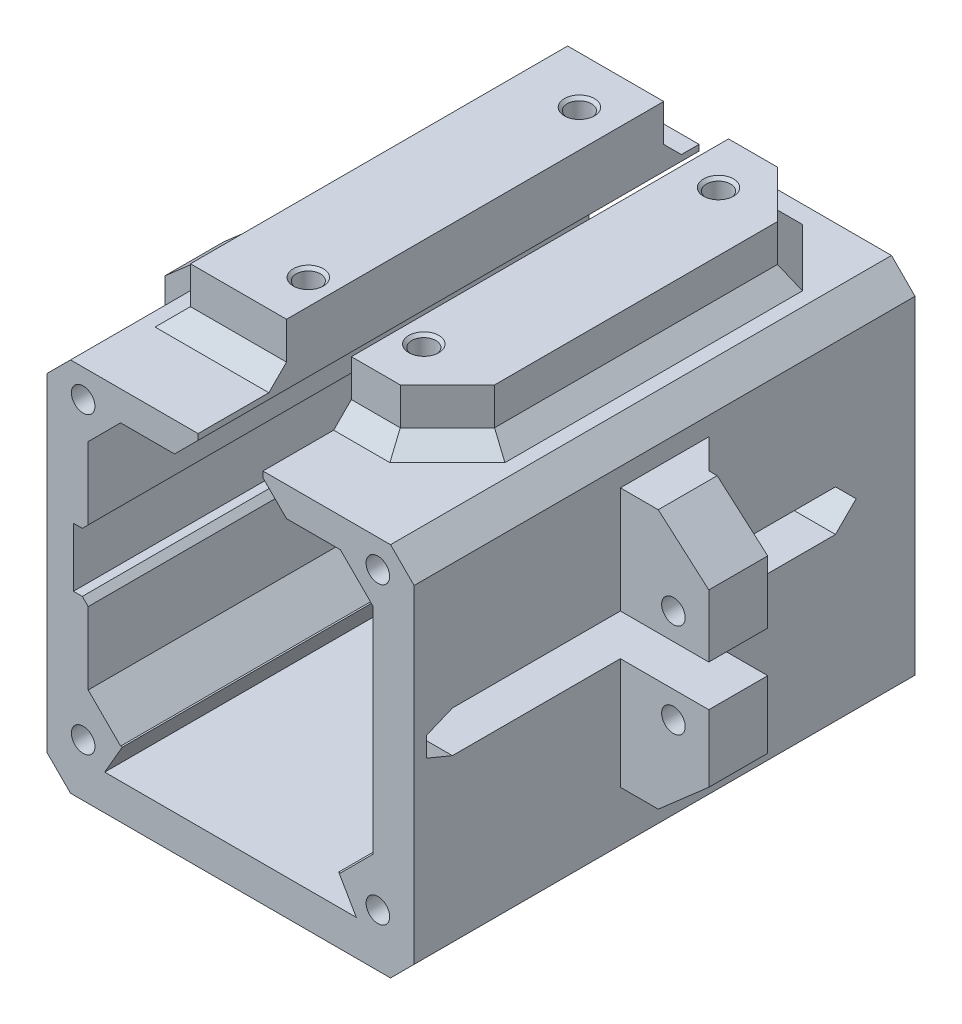
SolidWorks part; units mm, degrees
ref_plane "Front Plane" through (0, 0, 0) normal (0, 0, 1) x (1, 0, 0)
ref_plane "Top Plane" through (0, 0, 0) normal (0, 1, 0) x (1, 0, 0)
ref_plane "Right Plane" through (0, 0, 0) normal (1, 0, 0) x (0, 0, -1)
sketch "Sketch3" plane through (0, 0, 0) normal (0, 0, 1) x (1, 0, 0)
  line L0 (-20.15, 10.3748) -> (-23.65, 10.3748)
  line L1 (-23.65, 10.3748) -> (-23.65, 10.3393)
  line L2 (-23.65, 10.3393) -> (-18.1855, 4.8748)
  line L3 (-18.1855, 4.8748) -> (-21, 0)
  line L4 (-21, 0) -> (21, 0)
  line L5 (21, 0) -> (18.1855, 4.8748)
  line L6 (18.1855, 4.8748) -> (23.65, 10.3393)
  line L7 (23.65, 10.3393) -> (23.65, 10.3748)
  line L8 (23.65, 10.3748) -> (20.15, 10.3748)
  line L9 (20.15, 10.3748) -> (17.15, 7.3748)
  line L10 (17.15, 7.3748) -> (-17.15, 7.3748)
  line L11 (-17.15, 7.3748) -> (-20.15, 10.3748)
  point P12 (0, 0)
sketch "Sketch4" plane through (0, 0, 0) normal (0, 0, 1) x (1, 0, 0)
  line L3 (-18.3587, 4.9748) -> (-27, 4.9748)
  line L4 (-27, 4.9748) -> (-27, -6.2)
  line L5 (-27, -6.2) -> (27, -6.2)
  line L6 (21.3464, -0.2) -> (18.3587, 4.9748)
  line L7 (-21.3464, -0.2) -> (21.3464, -0.2)
  line L8 (-18.3587, 4.9748) -> (-21.3464, -0.2)
  line L9 (21.3464, -0.2) -> (18.3587, 4.9748)
  line L10 (-21.3464, -0.2) -> (21.3464, -0.2)
  line L11 (-18.3587, 4.9748) -> (-21.3464, -0.2)
  line L12 (27, -6.2) -> (27, 4.9748)
  line L13 (27, 4.9748) -> (18.3587, 4.9748)
  dimension "D2" = 36.7175
  dimension "D3" = 54
  dimension "D4" = 6
  dimension "D5" = 27
  dimension "D6" = 42.6928
  dimension "D7" = 60
  dimension "D8" = 11.1748
  dimension "D1" = 0.2
extrude "Boss-Extrude1" add sketch "Sketch4" along normal blind 100
sketch "Sketch6" plane through (0, 0, 100) normal (0, 0, 1) x (1, 0, 0)
  line L0 (-24.15, 4.9748) -> (-24.15, 52.4748)
  line L1 (-18.3587, 4.9748) -> (-27, 4.9748) construction
  line L2 (-24.15, 52.4748) -> (-5.5, 52.4748)
  line L3 (-5.5, 52.4748) -> (-5.5, 57.4748)
  line L4 (-5.5, 57.4748) -> (-31.15, 57.4748)
  line L5 (-31.15, 57.4748) -> (-31.15, -6.2)
  line L6 (-31.15, -6.2) -> (-24.15, -6.2)
  line L7 (-27, -6.2) -> (27, -6.2) construction
  line L8 (-24.15, -6.2) -> (-24.15, 4.9748)
  line L9 (-23.65, 46.5103) -> (-23.65, 34.3248) construction
  line L10 (-9, 51.9748) -> (-18.1855, 51.9748) construction
  line L12 (24.15, -6.2) -> (24.15, 52.4748)
  line L13 (-27, -6.2) -> (27, -6.2) construction
  line L14 (24.15, 52.4748) -> (5.5, 52.4748)
  line L15 (5.5, 52.4748) -> (5.5, 57.4748)
  line L16 (5.5, 57.4748) -> (31.15, 57.4748)
  line L17 (31.15, 57.4748) -> (31.15, -6.2)
  line L18 (31.15, -6.2) -> (24.15, -6.2)
  line L20 (23.65, 42.9748) -> (23.65, 46.5103) construction
  line L21 (5, 62.9748) -> (5, 55.9748) construction
  line L22 (-5, 55.9748) -> (-5, 62.9748) construction
  dimension "D1" = 7
  dimension "D2" = 0.5
  dimension "D3" = 0.5
  dimension "D4" = 5
  dimension "D5" = 0.5
  dimension "D6" = 5
  dimension "D7" = 0.5
  dimension "D8" = 7
  dimension "D9" = 0.5
extrude "Boss-Extrude2" add sketch "Sketch6" against normal up to surface (100 mm away) up to face at (0, 0.8874, 0)
sketch "Sketch7" plane through (31.15, 0, 0) normal (1, 0, 0) x (0, 0, -1)
  line L0 (-85, 28.7248) -> (-81.5, 25.2248)
  line L1 (-81.5, 25.2248) -> (-13.5, 25.2248)
  line L4 (-13.5, 32.2248) -> (-81.5, 32.2248)
  line L5 (-81.5, 32.2248) -> (-85, 28.7248)
  line L6 (-100, -6.2) -> (-100, 57.4748) construction
  line L7 (-13.5, 25.2248) -> (-10, 28.7248)
  line L8 (-10, 28.7248) -> (-13.5, 32.2248)
  line L9 (0, 57.4748) -> (0, -6.2) construction
  line L10 (-13.5, 25.2248) -> (0, 25.2248) construction
  line L11 (0, 32.2248) -> (-13.5, 32.2248) construction
  line L12 (0, 25.2248) -> (0, 32.2248) construction
  point P6 (0, 28.7248)
  dimension "D1" = 135
  dimension "D2" = 15
  dimension "D3" = 7
  dimension "D4" = 23.75
  dimension "D5" = 90
  dimension "D6" = 10
extrude "Cut-Extrude1" cut sketch "Sketch7" against normal blind 10
chamfer "Chamfer1" distance 5.5 angle 45 4 edges at (24.15, 4.9748, 50) (-24.15, 4.9748, 50) (-24.15, 52.4748, 50) (24.15, 52.4748, 50)
chamfer "Chamfer2" distance 4 angle 45 2 edges at (5.5, 52.4748, 50) (-5.5, 52.4748, 50)
sketch "Sketch8" plane through (0, 57.4748, 0) normal (0, 1, 0) x (1, 0, 0)
  line L0 (-5.5, -100) -> (-31.15, -100) construction
  line L1 (-21.8, -70) -> (13.8, -70)
  line L2 (-21.8, -70) -> (-21.8, -6)
  line L3 (-21.8, -6) -> (13.8, -6)
  line L4 (21.8, -62) -> (21.8, -14)
  line L5 (13.8, -70) -> (21.8, -62)
  line L6 (13.8, -6) -> (21.8, -14)
  circle A0 centre (9.8, -62) radius 2
  circle A1 centre (11.8, -14) radius 2
  circle A2 centre (-11.8, -14) radius 2
  circle A3 centre (-9.8, -62) radius 2
  point P1 (21.8, -6)
  point P3 (21.8, -70)
  dimension "D5" = 4
  dimension "D6" = 4
  dimension "D9" = 4
  dimension "D10" = 4
  dimension "D1" = 94
  dimension "D2" = 43.6
  dimension "D3" = 64
  dimension "D4" = 21.8
extrude "Boss-Extrude3" add sketch "Sketch8" along normal blind 9.3
sketch "Sketch9" plane through (0, 0, 0) normal (0, 0, 1) x (1, 0, 0)
  line L0 (-21.8, 66.7748) -> (13.8, 66.7748) construction
  line L1 (5.5, 57.4748) -> (-5.5, 57.4748)
  line L2 (5.5, 57.4748) -> (5.5, 66.7748)
  line L3 (5.5, 66.7748) -> (-5.5, 66.7748)
  line L4 (-5.5, 57.4748) -> (-5.5, 66.7748)
  line L5 (-5.5, 56.4748) -> (-5.5, 57.4748) construction
extrude "Cut-Extrude3" cut sketch "Sketch9" against normal blind 10 and the other way through all
chamfer "Chamfer3" distance 4 angle 45 4 edges at (31.15, -6.2, 50) (-31.15, -6.2, 50) (-31.15, 57.4748, 50) (31.15, 57.4748, 50)
chamfer "Chamfer4" distance 3 angle 45 8 edges at (9.65, 57.4748, 6) (17.8, 57.4748, 10) (21.8, 57.4748, 38) (17.8, 57.4748, 66) (9.65, 57.4748, 70) (-13.65, 57.4748, 6) (-13.65, 57.4748, 70) (-21.8, 57.4748, 38)
chamfer "Chamfer5" distance 3 3 edges at (27.65, 25.2248, 81.5) (27.65, 32.2248, 81.5) (27.65, 28.7248, 85)
sketch "Sketch10" plane through (0, 0, 100) normal (0, 0, 1) x (1, 0, 0)
  line L0 (-24.15, 10.4748) -> (-24.15, 46.9748) construction
  line L1 (-21.65, 23.7248) -> (-26.65, 23.7248)
  line L2 (-21.65, 23.7248) -> (-21.65, 33.7248)
  line L3 (-21.65, 33.7248) -> (-26.65, 33.7248)
  line L4 (-26.65, 23.7248) -> (-26.65, 33.7248)
  line L5 (-21.65, 23.7248) -> (-26.65, 33.7248) construction
  line L6 (-21.65, 33.7248) -> (-26.65, 23.7248) construction
  point P0 (-24.15, 28.7248)
  dimension "D1" = 5
  dimension "D2" = 10
extrude "Cut-Extrude4" cut sketch "Sketch10" against normal offset from surface (94 mm away) 6 up to face at (0, 29.896, 0)
chamfer "Chamfer7" distance 1 angle 45 1 edges at (-24.15, 28.7248, 6)
chamfer "Chamfer8" distance 1 angle 45 2 edges at (-24.15, 23.7248, 52.5) (-24.15, 33.7248, 52.5)
sketch "Sketch11" plane through (0, 66.7748, 0) normal (0, 1, 0) x (1, 0, 0)
  circle A0 centre (-11.8, -14) radius 2.05
  circle A1 centre (11.8, -14) radius 2.05
  circle A2 centre (-9.8, -62) radius 2.05
  circle A3 centre (9.8, -62) radius 2.05
  dimension "D1" = 4.1
  dimension "D2" = 4.1
  dimension "D3" = 4.1
  dimension "D4" = 4.1
extrude "Cut-Extrude5" cut sketch "Sketch11" against normal blind 10
chamfer "Chamfer9" distance 0.5 angle 45 4 edges at (11.8, 66.7748, 16.05) (-11.8, 66.7748, 16.05) (-9.8, 66.7748, 64.05) (9.8, 66.7748, 64.05)
sketch "Sketch12" plane through (0, 0, 100) normal (0, 0, 1) x (1, 0, 0)
  line L1 (-25, 52.7248) -> (25, 52.7248) construction
  line L2 (-25, 52.7248) -> (-25, 2.7248) construction
  line L3 (-25, 2.7248) -> (25, 2.7248) construction
  line L4 (25, 52.7248) -> (25, 2.7248) construction
  line L5 (24.15, 46.9748) -> (24.15, 10.4748) construction
  circle A0 centre (-25, 52.7248) radius 2
  circle A1 centre (25, 52.7248) radius 2
  circle A2 centre (-25, 2.7248) radius 2
  circle A3 centre (25, 2.7248) radius 2
  point P5 (0, 2.7248)
  point P9 (24.15, 28.7248)
  dimension "D1" = 4
  dimension "D5" = 4
  dimension "D6" = 4
  dimension "D7" = 4
  dimension "D2" = 50
  dimension "D3" = 50
  dimension "D4" = 24
extrude "Cut-Extrude6" cut sketch "Sketch12" against normal blind 30
ref_plane "Plane1" through (0, 0, 48) normal (0, 0, -1) x (-1, 0, 0)
sketch "Sketch16" plane through (0, 0, 48) normal (0, 0, -1) x (-1, 0, 0)
  line L1 (-22, -0.6752) -> (22, -0.6752)
  line L4 (22, -0.6752) -> (22, -9.2502)
  line L6 (-975.85, 28.3248) -> (49024.15, 28.3248) construction
  line L7 (24.15, 46.9748) -> (24.15, 10.4748) construction
  line L8 (22, -9.2502) -> (14.5, -17.8252)
  line L14 (-29, 50.3248) -> (-37.575, 50.3248)
  line L18 (0, -1000) -> (0, 49000) construction
  line L19 (0, 40.1361) -> (0, -40.1361) construction
  line L20 (-37.575, 50.3248) -> (-46.15, 42.8248)
  line L21 (-46.15, 42.8248) -> (-46.15, 13.8248)
  line L22 (-46.15, 13.8248) -> (-37.575, 6.3248)
  line L23 (-37.575, 6.3248) -> (-29, 6.3248)
  line L24 (-29, 6.3248) -> (-29, 50.3248)
  line L25 (37.575, 6.3248) -> (29, 6.3248)
  line L32 (14.5, -17.8252) -> (-14.5, -17.8252)
  line L33 (-14.5, -17.8252) -> (-22, -9.2502)
  line L34 (-22, -9.2502) -> (-22, -0.6752)
  line L42 (46.15, 13.8248) -> (37.575, 6.3248)
  line L43 (46.15, 42.8248) -> (46.15, 13.8248)
  line L44 (37.575, 50.3248) -> (46.15, 42.8248)
  line L45 (29, 50.3248) -> (37.575, 50.3248)
  line L46 (29, 6.3248) -> (29, 50.3248)
  line L47 (24.15, 4.1748) -> (-24.15, 4.1748) construction
  line L48 (24.15, 4.1748) -> (24.15, 52.4748) construction
  line L49 (24.15, 52.4748) -> (-24.15, 52.4748) construction
  line L50 (-24.15, 4.1748) -> (-24.15, 52.4748) construction
  line L51 (24.15, 4.1748) -> (-24.15, 52.4748) construction
  line L52 (24.15, 52.4748) -> (-24.15, 4.1748) construction
  line L53 (-18.65, 52.4748) -> (-9.5, 52.4748) construction
  point P18 (0, -0.6752)
  point P20 (0, -17.8252)
  point P32 (-46.15, 28.3248)
  point P33 (-29, 28.3248)
  point P34 (0, 28.3248)
  dimension "D1" = 44
  dimension "D2" = 29
  dimension "D3" = 17.15
  dimension "D4" = 8.575
  dimension "D5" = 29
  dimension "D6" = 29
  dimension "D7" = 8.575
  dimension "D8" = 17.15
  dimension "D9" = 29
  dimension "D10" = 44
  dimension "D11" = 48.3
  dimension "D12" = 48.3
extrude "Boss-Extrude6" add sketch "Sketch16" along normal blind 10 from offset 2 offset against normal yes
sketch "Sketch17" plane through (0, 0, 50) normal (0, 0, 1) x (1, 0, 0)
  line L0 (-975.85, 28.7248) -> (49024.15, 28.7248) construction
  line L1 (24.15, 46.9748) -> (24.15, 10.4748) construction
  line L3 (0, -1000.2) -> (0, 48999.8) construction
  line L4 (21.3464, -0.2) -> (-21.3464, -0.2) construction
  line L6 (0, -46.53) -> (0, 46.53) construction
  line L7 (-14.5, -17.8252) -> (14.5, -17.8252) construction
  line L8 (-46.15, 42.8248) -> (-46.15, 13.8248) construction
  circle A0 centre (-40.15, 36.7248) radius 2
  circle A1 centre (-40.15, 20.7248) radius 2
  circle A2 centre (40.15, 20.7248) radius 2
  circle A3 centre (40.15, 36.7248) radius 2
  circle A4 centre (-8, -11.8252) radius 2
  circle A5 centre (8, -11.8252) radius 2
  point P5 (24.15, 28.7248)
  point P14 (0, -0.2)
  dimension "D1" = 4
  dimension "D4" = 4
  dimension "D7" = 4
  dimension "D8" = 4
  dimension "D2" = 8
  dimension "D3" = 6
  dimension "D5" = 8
  dimension "D6" = 6
  dimension "D9" = 8
  dimension "D10" = 8
extrude "Cut-Extrude7" cut sketch "Sketch17" against normal blind 17.1
sketch "Sketch19" plane through (0, 0, 40) normal (0, 0, -1) x (-1, 0, 0)
  line L0 (-24.15, 25.2248) -> (-31.15, 25.2248) construction
  line L1 (-24.15, 32.2248) -> (-74.15, 32.2248)
  line L2 (-24.15, 32.2248) -> (-24.15, 25.2248)
  line L3 (-24.15, 25.2248) -> (-74.15, 25.2248)
  line L4 (-74.15, 32.2248) -> (-74.15, 25.2248)
  line L5 (-24.15, 10.4748) -> (-24.15, 46.9748) construction
  line L7 (-31.15, 32.2248) -> (-29, 32.2248) construction
  dimension "D1" = 50
extrude "Cut-Extrude13" cut sketch "Sketch19" against normal blind 17.1
sketch "Sketch20" plane through (0, 0, 100) normal (0, 0, 1) x (1, 0, 0)
  line L0 (31.15, -2.2) -> (31.15, 53.4748) construction
  line L1 (-31.15, 57.4748) -> (31.15, 57.4748)
  line L2 (-31.15, 57.4748) -> (-31.15, -6.2)
  line L3 (-31.15, -6.2) -> (31.15, -6.2)
  line L4 (31.15, 57.4748) -> (31.15, -6.2)
  line L5 (-5.5, 57.4748) -> (-27.15, 57.4748) construction
  line L6 (-31.15, 53.4748) -> (-31.15, -2.2) construction
  line L7 (-27.15, -6.2) -> (27.15, -6.2) construction
extrude "Cut-Extrude14" cut sketch "Sketch20" against normal blind 15
chamfer "Chamfer10" distance 5 angle 45 3 edges at (-31.15, 28.3248, 40) (31.15, 15.7748, 40) (31.15, 41.2748, 40)
chamfer "Chamfer11" distance 2 angle 45 1 edges at (0, -6.2, 40)
